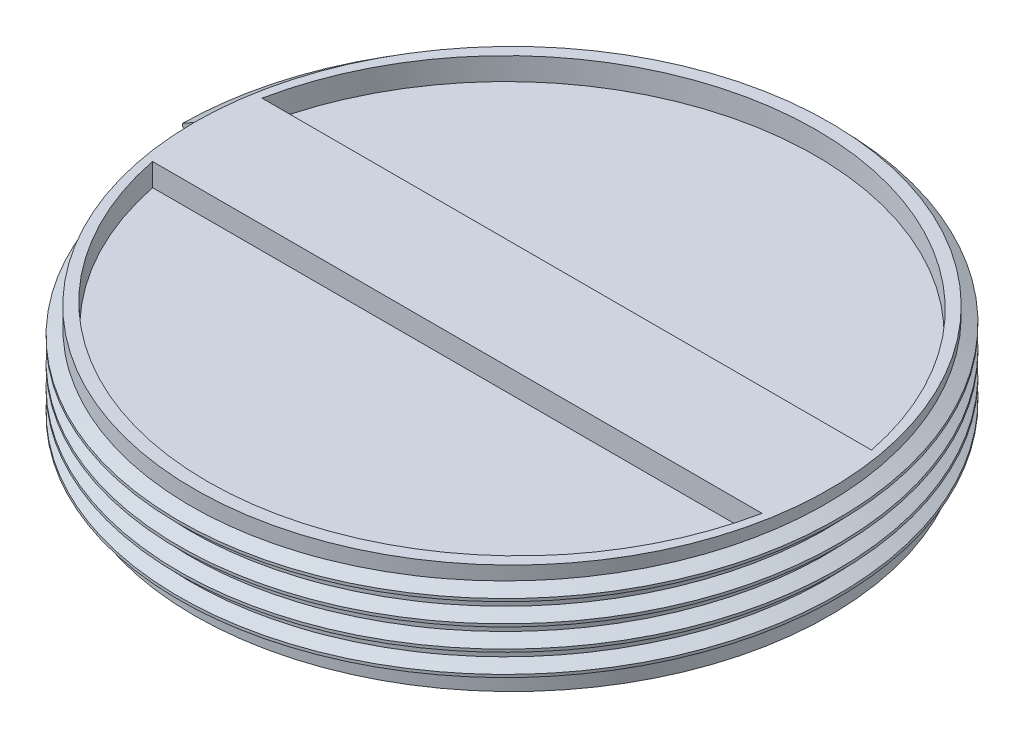
SolidWorks part; units mm, degrees
ref_plane "Front Plane" through (0, 0, 0) normal (0, 0, 1) x (1, 0, 0)
ref_plane "Top Plane" through (0, 0, 0) normal (0, 1, 0) x (1, 0, 0)
ref_plane "Right Plane" through (0, 0, 0) normal (1, 0, 0) x (0, 0, -1)
sketch "Sketch1" plane through (0, 0, 0) normal (0, 1, 0) x (1, 0, 0)
  circle A0 centre (0, 0) radius 29
  dimension "D1" = 58
extrude "Boss-Extrude2" add sketch "Sketch1" along normal blind 10
ref_plane "Plane1" through (0, 0, 45) normal (0, 0, 1) x (1, 0, 0)
thread "Thread1" pitch 2 method extrude profile "Thread Profile1" start angle 0, offset 0, length 8, pitch 2, diameter 58
ref_plane "Plane2" through (-29, 10, 0) normal (0, 0, 1) x (-1, 0, 0)
sketch "Thread Profile1" plane through (-29, 10, 0) normal (0, 0, 1) x (-1, 0, 0)
  line L0 (0, 0) -> (0, 2) construction
  line L1 (0, 0) -> (1.0825, 0.625)
  line L2 (1.0825, 0.625) -> (1.0825, 0.875)
  line L3 (1.0825, 0.875) -> (0, 1.5)
  line L4 (1.0825, 0.75) -> (0, 0.75) construction
  line L11 (0, 0) -> (0, 1.5)
  point P2 (0, 0)
  dimension "Pitch" = 2
  dimension "Profile_Angle" = 60
  dimension "Profile_Land" = 0.25
  dimension "Profile_Height" = 1.0825
ref_plane "Plane3" through (0, 0, 10) normal (0, 0, 1) x (1, 0, 0)
sketch "Sketch5" plane through (0, 10, 0) normal (0, 1, 0) x (1, 0, 0)
  line L0 (0, 0) -> (29, 0) construction
  line L1 (27.8215, 5) -> (-27.8215, 5) construction
  line L2 (27.8215, 5) -> (27.8215, -5) construction
  line L3 (27.8215, -5) -> (-27.8215, -5)
  line L4 (-27.8215, 5) -> (-27.8215, -5) construction
  line L5 (27.8215, 5) -> (-27.8215, -5) construction
  line L6 (27.8215, -5) -> (-27.8215, 5) construction
  arc A0 (-27.8215, -5) -> (27.8215, -5) centre (0, 0.576) ccw
  circle A1 centre (0, 0) radius 29 construction
  point P0 (0, 0)
  point P12 (-29.977, -5)
  dimension "D1" = 10
  dimension "D2" = 5
  dimension "D3" = 5
extrude "Cut-Extrude2" cut sketch "Sketch5" against normal blind 2 draft 2
mirror "Mirror1" about plane through (0, 0, 0) normal (0, 0, 1) of "Cut-Extrude2"
